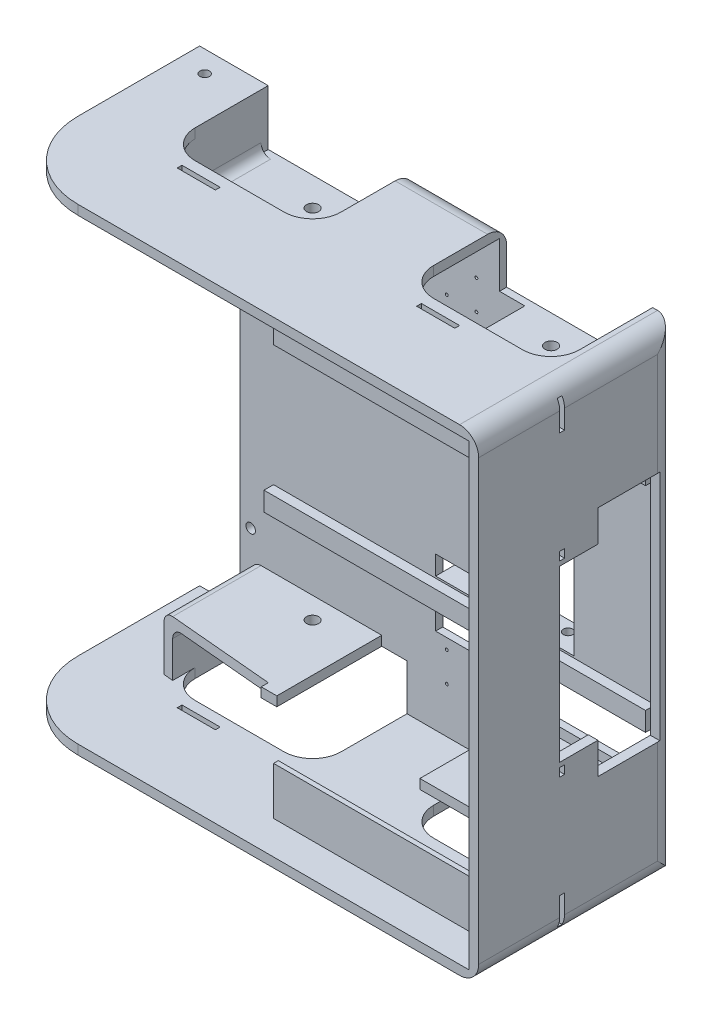
SolidWorks part; units mm, degrees
ref_plane "Front Plane" through (0, 0, 0) normal (0, 0, 1) x (1, 0, 0)
ref_plane "Top Plane" through (0, 0, 0) normal (0, 1, 0) x (1, 0, 0)
ref_plane "Right Plane" through (0, 0, 0) normal (1, 0, 0) x (0, 0, -1)
sketch "Sketch2" plane through (0, 0, 0) normal (0, 0, 1) x (1, 0, 0)
  line L2 (-250, -250) -> (250, -250)
  line L3 (-250, -250) -> (-250, 250)
  line L4 (-250, 250) -> (250, 250)
  line L5 (250, -250) -> (250, 250)
  line L6 (-250, -250) -> (250, 250) construction
  line L11 (-250, 250) -> (250, -250) construction
  dimension "D12" = 500
  dimension "D13" = 500
extrude "Boss-Extrude1" add sketch "Sketch2" along normal blind 7.5
sketch "Sketch3" plane through (0, 0, 7.5) normal (0, 0, 1) x (1, 0, 0)
  line L0 (-250, 250) -> (-250, 240)
  line L1 (-250, 250) -> (-250, -250) construction
  line L2 (-250, 240) -> (-240, 240)
  line L3 (-240, -240) -> (-250, -240)
  line L4 (-250, -240) -> (-250, -250)
  line L8 (240, -240) -> (240, 240)
  line L9 (240, 240) -> (-240, 240)
  line L10 (-240, 240) -> (-240, -240)
  line L11 (-240, -240) -> (240, -240)
  line L12 (240, -240) -> (240, 240)
  line L13 (240, 240) -> (-240, 240)
  line L15 (-240, -240) -> (240, -240)
  line L16 (250, -250) -> (250, 250)
  line L17 (250, 250) -> (-250, 250)
  line L18 (-250, 250) -> (-250, -250)
  line L19 (-250, -250) -> (250, -250)
  line L20 (250, -250) -> (250, 250)
  line L21 (250, 250) -> (-250, 250)
  line L23 (-250, -250) -> (250, -250)
  dimension "D1" = 10
  dimension "D2" = 0
extrude "Boss-Extrude2" add sketch "Sketch3" along normal blind 200
sketch "Sketch4" plane through (0, 0, 7.5) normal (0, 0, 1) x (1, 0, 0)
  line L0 (-328.6377, 0) -> (350.8287, 0) construction
  line L1 (148.4, 192) -> (148.4, 0) construction
  line L2 (98.4, 192) -> (198.4, 192)
  line L3 (98.4, 192) -> (98.4, 182)
  line L4 (98.4, 182) -> (198.4, 182)
  line L5 (198.4, 192) -> (198.4, 182)
  line L6 (98.4, -192) -> (98.4, -182)
  line L7 (98.4, -192) -> (198.4, -192)
  line L8 (250, -250) -> (250, 250) construction
  line L9 (250, 250) -> (-250, 250) construction
  line L10 (198.4, -192) -> (198.4, -182)
  line L11 (98.4, -182) -> (198.4, -182)
  line L12 (-151.6, 192) -> (-51.6, 192)
  line L13 (-151.6, 192) -> (-151.6, 182)
  line L14 (-151.6, 182) -> (-51.6, 182)
  line L15 (-51.6, 192) -> (-51.6, 182)
  line L16 (-151.6, -182) -> (-51.6, -182)
  line L17 (-51.6, -192) -> (-51.6, -182)
  line L18 (-151.6, -192) -> (-51.6, -192)
  line L19 (-151.6, -192) -> (-151.6, -182)
  dimension "D1" = 100
  dimension "D2" = 101.6
  dimension "D3" = 58
  dimension "D5" = 10
  dimension "D4" = 2
extrude "Boss-Extrude3" add sketch "Sketch4" along normal blind 110
sketch "Sketch5" plane through (0, 250, 0) normal (0, 1, 0) x (1, 0, 0)
  line L0 (148.4, 0) -> (148.4, -196.9902) construction
  line L1 (-250, 0) -> (250, 0) construction
  line L2 (250, -207.5) -> (250, 0) construction
  line L3 (71.9, 46.5) -> (224.9, 46.5)
  line L4 (71.9, 46.5) -> (71.9, -76.5)
  line L5 (101.9, -106.5) -> (194.9, -106.5)
  line L6 (224.9, 46.5) -> (224.9, -76.5)
  line L7 (71.9, 46.5) -> (224.9, -106.5) construction
  line L8 (71.9, -106.5) -> (224.9, 46.5) construction
  line L9 (0, 0) -> (0, -207.5) construction
  line L10 (-250, -207.5) -> (250, -207.5) construction
  line L11 (-178.1, 46.5) -> (-178.1, -76.5)
  line L12 (-178.1, 46.5) -> (-25.1, 46.5)
  line L13 (-25.1, 46.5) -> (-25.1, -76.5)
  line L14 (-148.1, -106.5) -> (-55.1, -106.5)
  arc A0 (194.9, -106.5) -> (224.9, -76.5) centre (194.9, -76.5) ccw
  arc A1 (71.9, -76.5) -> (101.9, -106.5) centre (101.9, -76.5) ccw
  arc A2 (-55.1, -106.5) -> (-25.1, -76.5) centre (-55.1, -76.5) ccw
  arc A3 (-178.1, -76.5) -> (-148.1, -106.5) centre (-148.1, -76.5) ccw
  point P4 (148.4, -30)
  dimension "D5" = 30
  dimension "D1" = 153
  dimension "D2" = 153
  dimension "D3" = 2
  dimension "D4" = 101.6
extrude "Cut-Extrude3" cut sketch "Sketch5" against normal up to surface (58 mm away) up to face at (148.4, 192, 62.5)
sketch "Sketch6" plane through (0, -250, 0) normal (0, -1, 0) x (1, 0, 0)
  line L4 (224.9, 0) -> (71.9, 0) construction
  line L5 (71.9, 0) -> (71.9, 76.5) construction
  line L6 (101.9, 106.5) -> (194.9, 106.5) construction
  line L7 (224.9, 76.5) -> (224.9, 0) construction
  line L8 (-25.1, 0) -> (-178.1, 0) construction
  line L9 (-178.1, 0) -> (-178.1, 76.5) construction
  line L10 (-148.1, 106.5) -> (-55.1, 106.5) construction
  line L11 (-25.1, 76.5) -> (-25.1, 0) construction
  line L12 (224.9, 0) -> (71.9, 0)
  line L13 (71.9, 0) -> (71.9, 76.5)
  line L14 (101.9, 106.5) -> (194.9, 106.5)
  line L15 (224.9, 76.5) -> (224.9, 0)
  line L16 (-25.1, 0) -> (-178.1, 0)
  line L17 (-178.1, 0) -> (-178.1, 76.5)
  line L18 (-148.1, 106.5) -> (-55.1, 106.5)
  line L19 (-25.1, 76.5) -> (-25.1, 0)
  arc A2 (101.9, 106.5) -> (71.9, 76.5) centre (101.9, 76.5) ccw construction
  arc A3 (224.9, 76.5) -> (194.9, 106.5) centre (194.9, 76.5) ccw construction
  arc A4 (-148.1, 106.5) -> (-178.1, 76.5) centre (-148.1, 76.5) ccw construction
  arc A5 (-25.1, 76.5) -> (-55.1, 106.5) centre (-55.1, 76.5) ccw construction
  arc A6 (101.9, 106.5) -> (71.9, 76.5) centre (101.9, 76.5) ccw
  arc A7 (224.9, 76.5) -> (194.9, 106.5) centre (194.9, 76.5) ccw
  arc A8 (-148.1, 106.5) -> (-178.1, 76.5) centre (-148.1, 76.5) ccw
  arc A9 (-25.1, 76.5) -> (-55.1, 106.5) centre (-55.1, 76.5) ccw
extrude "Cut-Extrude4" cut sketch "Sketch6" against normal blind 58
sketch "Sketch7" plane through (0, -182, 0) normal (0, 1, 0) x (1, 0, 0)
  line L0 (224.9, 0) -> (71.9, 0) construction
  circle A0 centre (148.4, -30) radius 6.35
  circle A1 centre (-101.6, -30) radius 6.35
  dimension "D1" = 12.7
  dimension "D2" = 30
  dimension "D3" = 2
extrude "Cut-Extrude5" cut sketch "Sketch7" against normal mid plane 1000
sketch "Sketch8" plane through (0, 0, 7.5) normal (0, 0, 1) x (1, 0, 0)
  line L0 (224.9, 240) -> (224.9, 192) construction
  line L2 (224.9, 192) -> (198.4, 192) construction
  line L3 (84.9, 172) -> (234.9, 172)
  line L4 (84.9, 172) -> (84.9, 122)
  line L5 (84.9, 122) -> (234.9, 122)
  line L6 (234.9, 172) -> (234.9, 122)
  line L7 (0, 0) -> (250, 0) construction
  line L8 (250, -250) -> (250, 250) construction
  line L9 (234.9, -172) -> (234.9, -122)
  line L10 (84.9, -172) -> (234.9, -172)
  line L11 (84.9, -172) -> (84.9, -122)
  line L12 (84.9, -122) -> (234.9, -122)
  point P3 (224.9, 216)
  point P11 (211.65, 192)
  dimension "D1" = 150
  dimension "D2" = 50
  dimension "D3" = 20
  dimension "D4" = 10
extrude "Cut-Extrude6" cut sketch "Sketch8" against normal blind 10
sketch "Sketch11" plane through (0, -182, 0) normal (0, 1, 0) x (1, 0, 0)
  line L0 (-151.6, -117.5) -> (-91.6, -117.5)
  line L1 (-51.6, -117.5) -> (-151.6, -117.5) construction
  line L2 (-91.6, -117.5) -> (-67.9827, -117.5)
  line L3 (-151.6, -117.5) -> (-151.6, -7.5) construction
  line L4 (-151.6, -102.5) -> (-151.6, -117.5)
  line L7 (-67.9827, -117.5) -> (-67.9827, -110)
  line L8 (-67.9827, -110) -> (-151.6, -102.5)
  dimension "D1" = 15
  dimension "D2" = 60
extrude "Cut-Extrude9" cut sketch "Sketch11" against normal blind 10
mirror "Mirror1" about plane through (0, 0, 0) normal (0, 1, 0) of "Cut-Extrude9"
sketch "Sketch12" plane through (0, 0, 7.5) normal (0, 0, 1) x (1, 0, 0)
  line L0 (-250, 0) -> (240, 0) construction
  line L1 (-250, 240) -> (-250, -240) construction
  line L2 (240, 240) -> (240, -240) construction
  line L3 (100, -120) -> (100, -100)
  line L4 (100, 120) -> (150, 120)
  line L5 (100, 120) -> (100, 100)
  line L6 (100, 100) -> (150, 100)
  line L7 (150, 120) -> (150, 100)
  line L8 (100, -120) -> (150, -120)
  line L9 (150, -120) -> (150, -100)
  line L10 (100, -100) -> (150, -100)
  dimension "D1" = 20
  dimension "D2" = 50
  dimension "D3" = 100
  dimension "D4" = 100
extrude "Boss-Extrude4" add sketch "Sketch12" against normal blind 30
sketch "Sketch13" plane through (0, 100, 0) normal (0, -1, 0) x (1, 0, 0)
  line L0 (125, 0) -> (125, -22.5) construction
  line L1 (150, 0) -> (100, 0) construction
  line L2 (100, -22.5) -> (150, -22.5) construction
  circle A0 centre (125, -11.25) radius 5
  dimension "D1" = 10
extrude "Cut-Extrude10" cut sketch "Sketch13" against normal mid plane 1000
sketch "Sketch14" plane through (0, 0, 0) normal (0, 0, -1) x (-1, 0, 0)
  line L0 (-125, 100) -> (-125, -100) construction
  line L1 (-150, 100) -> (-100, 100) construction
  line L2 (-100, -100) -> (-150, -100) construction
  line L3 (-84.9, -122) -> (-84.9, -172) construction
  line L4 (-150, -100) -> (-100, -100)
  line L5 (-150, -100) -> (-150, 100)
  line L6 (-150, 100) -> (-100, 100)
  line L9 (-4.9, -130) -> (-4.9, -150)
  line L10 (-250, 0) -> (250, 0) construction
  line L11 (-100, 100) -> (-90.1659, 100)
  line L12 (-150, 90) -> (61.6959, 90) construction
  line L13 (-4.9, -80) -> (-4.9, -100)
  line L14 (-54.9, 80) -> (-4.9, 80)
  line L15 (-54.9, 80) -> (-54.9, 100)
  line L16 (-54.9, 100) -> (-4.9, 100)
  line L17 (-250, -250) -> (-250, 250) construction
  line L18 (250, 250) -> (250, -250) construction
  line L19 (-4.9, 80) -> (-4.9, 100)
  line L20 (-54.9, 80) -> (-4.9, 100) construction
  line L21 (-54.9, 100) -> (-4.9, 80) construction
  line L22 (-54.9, -100) -> (-4.9, -100)
  line L23 (-54.9, -80) -> (-54.9, -100)
  line L24 (-54.9, -80) -> (-4.9, -80)
  line L25 (-54.9, -150) -> (-4.9, -150)
  line L26 (-54.9, -130) -> (-54.9, -150)
  line L27 (-54.9, -130) -> (-4.9, -130)
  line L28 (-4.9, 130) -> (-4.9, 150)
  line L29 (-54.9, 130) -> (-4.9, 130)
  line L30 (-54.9, 130) -> (-54.9, 150)
  line L31 (-54.9, 150) -> (-4.9, 150)
  line L33 (-100, -100) -> (-90.1659, -100)
  line L34 (-90.1659, 100) -> (-90.1659, -100)
  point P6 (-125, 0)
  point P13 (-125, 144.1305)
  point P26 (-29.9, 90)
  dimension "D1" = 0
  dimension "D2" = 10
  dimension "D3" = 20
  dimension "D4" = 50
  dimension "D5" = 30
  dimension "D6" = 2
extrude "Cut-Extrude11" cut sketch "Sketch14" against normal blind 1000
sketch "Sketch15" plane through (0, 0, 7.5) normal (0, 0, 1) x (1, 0, 0)
  line L0 (-250, 0) -> (250, 0) construction
  line L1 (234.9, 122) -> (-165.0265, 122)
  line L2 (234.9, 122) -> (234.9, 102)
  line L3 (234.9, 102) -> (-165.0265, 102)
  line L4 (-165.0265, 122) -> (-165.0265, 102)
  line L5 (-250, 240) -> (-250, -240) construction
  line L6 (250, -250) -> (250, 250) construction
  line L7 (234.9, -122) -> (234.9, -102)
  line L8 (-165.0265, -122) -> (-165.0265, -102)
  line L9 (234.9, -102) -> (-165.0265, -102)
  line L10 (234.9, -122) -> (-165.0265, -122)
  dimension "D1" = 20
extrude "Boss-Extrude5" add sketch "Sketch15" along normal blind 10
sketch "Sketch16" plane through (0, 250, 0) normal (0, 1, 0) x (1, 0, 0)
  line L0 (-250, -207.5) -> (-250, 0) construction
  line L1 (250, -207.5) -> (-250, -207.5) construction
  line L2 (-250, -127.5) -> (-250, 0)
  line L3 (250, -207.5) -> (-170, -207.5)
  line L4 (250, -207.5) -> (250, -261.6266)
  line L5 (250, -261.6266) -> (-350.3423, -261.6266)
  line L6 (-350.3423, -261.6266) -> (-350.3423, 0)
  line L7 (-350.3423, 0) -> (-250, 0)
  arc A0 (-250, -127.5) -> (-170, -207.5) centre (-170, -127.5) ccw
  dimension "D1" = 80
extrude "Cut-Extrude12" cut sketch "Sketch16" against normal blind 500
sketch "Sketch17" plane through (0, 0, 7.5) normal (0, 0, 1) x (1, 0, 0)
  line L0 (-200, 240) -> (-200, -240)
  line L1 (-250, -240) -> (-200, -240)
  line L2 (-250, -240) -> (-250, 240)
  line L3 (-250, 240) -> (-200, 240)
  line L4 (-250, 250) -> (-250, -250) construction
  dimension "D1" = 50
extrude "Cut-Extrude13" cut sketch "Sketch17" against normal blind 500
fillet "Fillet2" radius 20 5 edges at (23.4, -250, 0) (23.4, 250, 0) (250, 0, 0) (250, -250, 103.75) (250, 250, 103.75)
sketch "Sketch18" plane through (240, 0, 0) normal (-1, 0, 0) x (0, 0, 1)
  line L0 (0, 0) -> (122.5, 0) construction
  line L1 (17.5, 122) -> (82.5, 122)
  line L2 (82.5, -89) -> (82.5, -122)
  line L3 (17.5, -122) -> (82.5, -122)
  line L4 (82.5, 122) -> (82.5, 89)
  line L5 (17.5, -122) -> (17.5, 122)
  line L6 (82.5, 89) -> (122.5, 89)
  line L8 (82.5, -89) -> (122.5, -89)
  line L9 (122.5, 89) -> (122.5, -89)
  dimension "D1" = 178
  dimension "D2" = 244
  dimension "D3" = 89
  dimension "D4" = 40
  dimension "D5" = 65
extrude "Cut-Extrude14" cut sketch "Sketch18" against normal blind 38
sketch "Sketch19" plane through (0, 0, 7.5) normal (0, 0, 1) x (1, 0, 0)
  line L0 (0, 0) -> (-200, 0) construction
  line L1 (-200, -240) -> (-200, 240) construction
  line L2 (-178.1, 250) -> (-250, 250) construction
  line L3 (-250, 250) -> (-250, 240) construction
  circle A0 centre (-189, 153.5) radius 5
  circle A1 centre (-189, -153.5) radius 5
  point P13 (-250, 245)
  dimension "D3" = 10
  dimension "D1" = 96.5
  dimension "D2" = 61
extrude "Cut-Extrude15" cut sketch "Sketch19" against normal blind 10
sketch "Sketch20" plane through (0, 0, 7.5) normal (0, 0, 1) x (1, 0, 0)
  line L0 (-178.1, 240) -> (-178.1, 202)
  line L1 (-168.1, 192) -> (-151.6, 192)
  line L2 (-151.6, 192) -> (-151.6, 182)
  line L3 (-151.6, 182) -> (-178.1, 182)
  line L4 (-188.1, 192) -> (-188.1, 240)
  line L5 (-250, 240) -> (-170, 240) construction
  line L6 (-188.1, 240) -> (-178.1, 240)
  arc A0 (-178.1, 182) -> (-188.1, 192) centre (-178.1, 192) cw
  arc A1 (-178.1, 202) -> (-168.1, 192) centre (-168.1, 202) ccw
  point P16 (-178.1, 192)
  dimension "D2" = 10
  dimension "D3" = 10
  dimension "D1" = 10
extrude "Boss-Extrude6" add sketch "Sketch20" along normal up to surface (91.7262 mm away) up to face at (-109.7913, 187, 106.25)
mirror "Mirror2" about plane through (0, 0, 0) normal (0, 1, 0) of "Boss-Extrude6"
sketch "Sketch21" plane through (0, -240, 0) normal (0, 1, 0) x (1, 0, 0)
  circle A0 centre (-222.1748, -22.5) radius 5
extrude "Cut-Extrude16" cut sketch "Sketch21" against normal mid plane 1000
sketch "Sketch22" plane through (0, -250, 0) normal (0, -1, 0) x (1, 0, 0)
  line L1 (-151, 122.5) -> (-111, 122.5)
  line L2 (-151, 122.5) -> (-151, 117.5)
  line L3 (-151, 117.5) -> (-111, 117.5)
  line L4 (-111, 122.5) -> (-111, 117.5)
  line L5 (100, 122.5) -> (140, 122.5)
  line L6 (100, 122.5) -> (100, 117.5)
  line L7 (100, 117.5) -> (140, 117.5)
  line L8 (140, 122.5) -> (140, 117.5)
extrude "Cut-Extrude17" cut sketch "Sketch22" against normal blind 1000
sketch "Sketch23" plane through (250, 0, 0) normal (1, 0, 0) x (0, 0, -1)
  line L1 (-122.5, -240) -> (-117.5, -240)
  line L2 (-122.5, -240) -> (-122.5, -210)
  line L3 (-122.5, -210) -> (-117.5, -210)
  line L4 (-117.5, -240) -> (-117.5, -210)
  line L5 (-122.5, -102.5) -> (-117.5, -102.5)
  line L6 (-122.5, -102.5) -> (-122.5, -93.75)
  line L7 (-122.5, -93.75) -> (-117.5, -93.75)
  line L8 (-117.5, -102.5) -> (-117.5, -93.75)
  line L9 (-122.5, 93.75) -> (-117.5, 93.75)
  line L10 (-122.5, 93.75) -> (-122.5, 102.5)
  line L11 (-122.5, 102.5) -> (-117.5, 102.5)
  line L12 (-117.5, 93.75) -> (-117.5, 102.5)
  line L13 (-122.5, 210) -> (-117.5, 210)
  line L14 (-122.5, 210) -> (-122.5, 240)
  line L15 (-122.5, 240) -> (-117.5, 240)
  line L16 (-117.5, 210) -> (-117.5, 240)
extrude "Cut-Extrude18" cut sketch "Sketch23" against normal blind 20
sketch "Sketch25" plane through (0, 0, 7.5) normal (0, 0, 1) x (1, 0, 0)
  line L0 (342.7479, 0) -> (-342.7479, 0) construction
  circle A0 centre (16.625, -161.1305) radius 1.5
  circle A1 centre (47.625, -161.1305) radius 1.5
  circle A2 centre (47.625, -192.1305) radius 1.5
  circle A3 centre (16.625, -192.1305) radius 1.5
  circle A4 centre (16.625, 192.1305) radius 1.5
  circle A5 centre (47.625, 192.1305) radius 1.5
  circle A6 centre (47.625, 161.1305) radius 1.5
  circle A7 centre (16.625, 161.1305) radius 1.5
  dimension "D1" = 3
  dimension "D2" = 2
  dimension "D3" = 2
extrude "Cut-Extrude19" cut sketch "Sketch25" against normal blind 50
sketch "Sketch26" plane through (0, 0, 0) normal (0, 0, -1) x (-1, 0, 0)
  line L1 (-54.9, 100) -> (-4.9, 100)
  line L2 (-54.9, 100) -> (-54.9, 120)
  line L3 (-54.9, 120) -> (-4.9, 120)
  line L4 (-4.9, 100) -> (-4.9, 120)
  line L5 (-54.9, -100) -> (-4.9, -100)
  line L6 (-54.9, -100) -> (-54.9, -120)
  line L7 (-54.9, -120) -> (-4.9, -120)
  line L8 (-4.9, -100) -> (-4.9, -120)
  dimension "D1" = 50
  dimension "D2" = 50
  dimension "D3" = 20
  dimension "D4" = 20
extrude "Boss-Extrude7" add sketch "Sketch26" along normal up to surface (22.5 mm away) up to face at (125, 110, -22.5)
sketch "Sketch28" plane through (0, 120, 0) normal (0, 1, 0) x (1, 0, 0)
  line L0 (125, 11.25) -> (29.9, 11.25) construction
  line L1 (29.9, 22.5) -> (29.9, 0) construction
  line L2 (54.9, 22.5) -> (4.9, 22.5) construction
  line L3 (4.9, 0) -> (54.9, 0) construction
  circle A0 centre (29.9, 11.25) radius 5
  dimension "D1" = 10
extrude "Cut-Extrude20" cut sketch "Sketch28" against normal blind 250
sketch "Sketch29" plane through (0, -240, 0) normal (0, 1, 0) x (1, 0, 0)
  line L0 (240, -207.5) -> (240, -122.5) construction
  line L1 (0, -172.5) -> (240, -172.5)
  line L2 (0, -172.5) -> (0, -167.5)
  line L3 (0, -167.5) -> (240, -167.5)
  line L4 (240, -172.5) -> (240, -167.5)
  line L5 (240, -207.5) -> (-170, -207.5) construction
  dimension "D1" = 5
  dimension "D2" = 240
  dimension "D3" = 35
extrude "Boss-Extrude8" add sketch "Sketch29" along normal blind 50
mirror "Mirror3" about plane through (0, 0, 0) normal (0, 1, 0) of "Boss-Extrude8"
